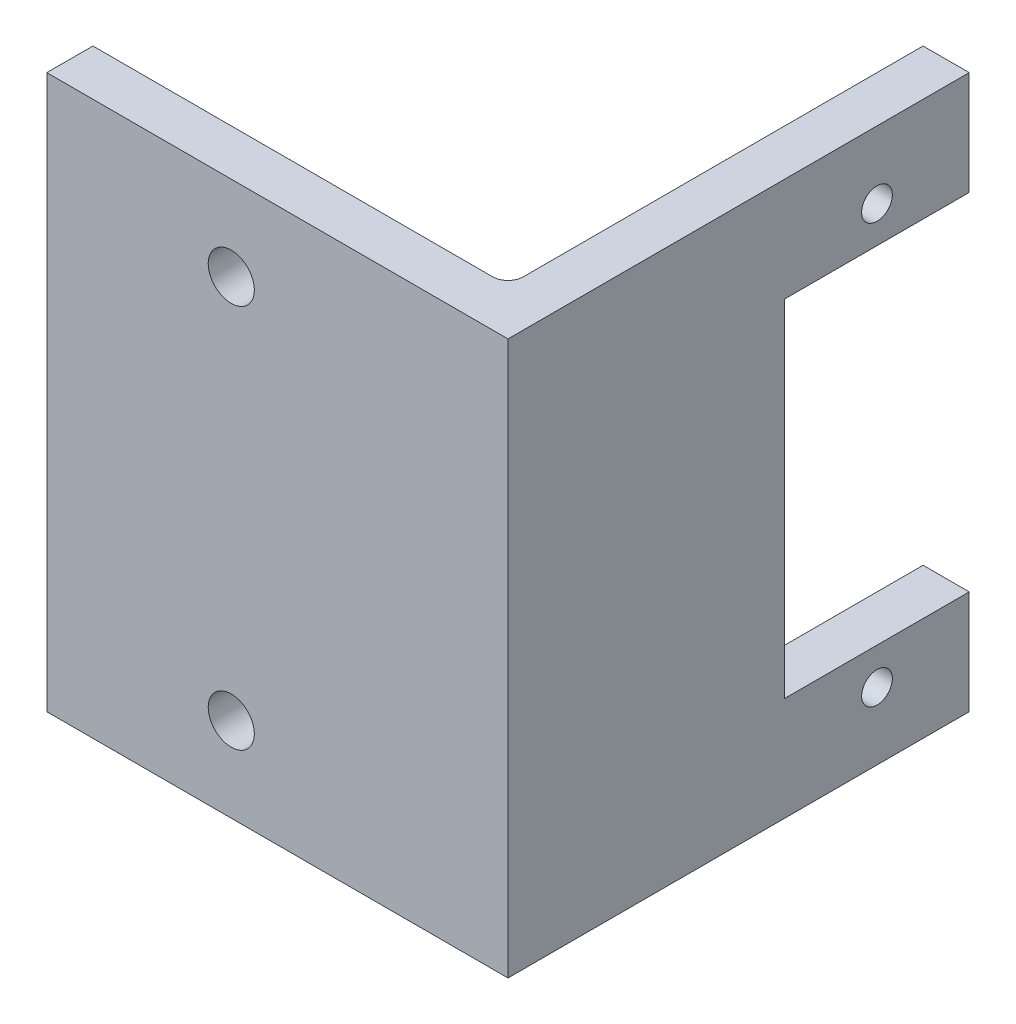
SolidWorks part; units mm, degrees
ref_plane "Front Plane" through (0, 0, 0) normal (0, 0, 1) x (1, 0, 0)
ref_plane "Top Plane" through (0, 0, 0) normal (0, 1, 0) x (1, 0, 0)
ref_plane "Right Plane" through (0, 0, 0) normal (1, 0, 0) x (0, 0, -1)
sketch "Sketch1" plane through (0, 0, 0) normal (0, 1, 0) x (1, 0, 0)
  line L0 (0, 0) -> (0, 30)
  line L1 (0, 0) -> (-30, 0)
  dimension "D1" = 30
extrude "Extrude-Thin1" add sketch "Sketch1" along normal mid plane 36 thin thin type one direction wall 3
sketch "Sketch2" plane through (0, 0, 0) normal (1, 0, 0) x (0, 0, -1)
  line L0 (0, 0) -> (36.7713, 0) construction
  line L1 (30, 18) -> (30, -18) construction
  line L2 (18, 11.25) -> (30, 11.25)
  line L3 (18, 11.25) -> (18, -11.25)
  line L4 (18, -11.25) -> (30, -11.25)
  line L5 (30, 11.25) -> (30, -11.25)
  line L6 (18, 11.25) -> (30, -11.25) construction
  line L7 (18, -11.25) -> (30, 11.25) construction
  line L8 (24, 13.625) -> (24, -13.625) construction
  circle A0 centre (24, 13.625) radius 1
  circle A1 centre (24, -13.625) radius 1
  point P3 (24, 0)
  dimension "D3" = 2
  dimension "D1" = 12
  dimension "D2" = 22.5
  dimension "D4" = 27.25
extrude "Cut-Extrude1" cut sketch "Sketch2" against normal blind 10
sketch "Sketch3" plane through (0, 0, -3) normal (0, 0, -1) x (-1, 0, 0)
  line L0 (3, 18) -> (3, -18) construction
  line L1 (3, 2) -> (25, 2)
  line L2 (3, 2) -> (3, -2)
  line L3 (3, -2) -> (25, -2)
  line L4 (25, 2) -> (25, -2)
  line L5 (0, 0) -> (43.5118, 0) construction
  dimension "D1" = 22
  dimension "D2" = 4
extrude "Boss-Extrude1" add sketch "Sketch3" along normal blind 15
sketch "Sketch4" plane through (0, 2, 0) normal (0, 1, 0) x (1, 0, 0)
  line L0 (-25, 3) -> (-10, 18)
  line L1 (-25, 18) -> (-3, 18) construction
  line L2 (-10, 18) -> (-25, 18)
  line L3 (-25, 18) -> (-25, 3)
  dimension "D1" = 15
extrude "Cut-Extrude2" cut sketch "Sketch4" against normal blind 15
fillet "Fillet1" radius 1 4 edges at (-3, -2, -10.5) (-17.5, -2, -10.5) (-3, 2, -10.5) (-17.5, 2, -10.5)
fillet "Fillet2" radius 1 9 edges at (-3, -10.5, -3) (-3.2929, -2.2929, -3) (-13.7929, -2, -3) (-24.5858, -1.7071, -3) (-25, 0, -3) (-24.5858, 1.7071, -3) (-13.7929, 2, -3) (-3.2929, 2.2929, -3) (-3, 10.5, -3)
sketch "Sketch5" plane through (0, 0, -3) normal (0, 0, -1) x (-1, 0, 0)
  line L0 (0, 0) -> (35.4788, 0) construction
  line L1 (18, -12.5) -> (18, 12.5) construction
  line L2 (30, 18) -> (30, -18) construction
  circle A0 centre (18, -12.5) radius 1.5
  circle A1 centre (18, 12.5) radius 1.5
  dimension "D1" = 3
  dimension "D2" = 12
  dimension "D3" = 25
extrude "Cut-Extrude3" cut sketch "Sketch5" against normal blind 15
